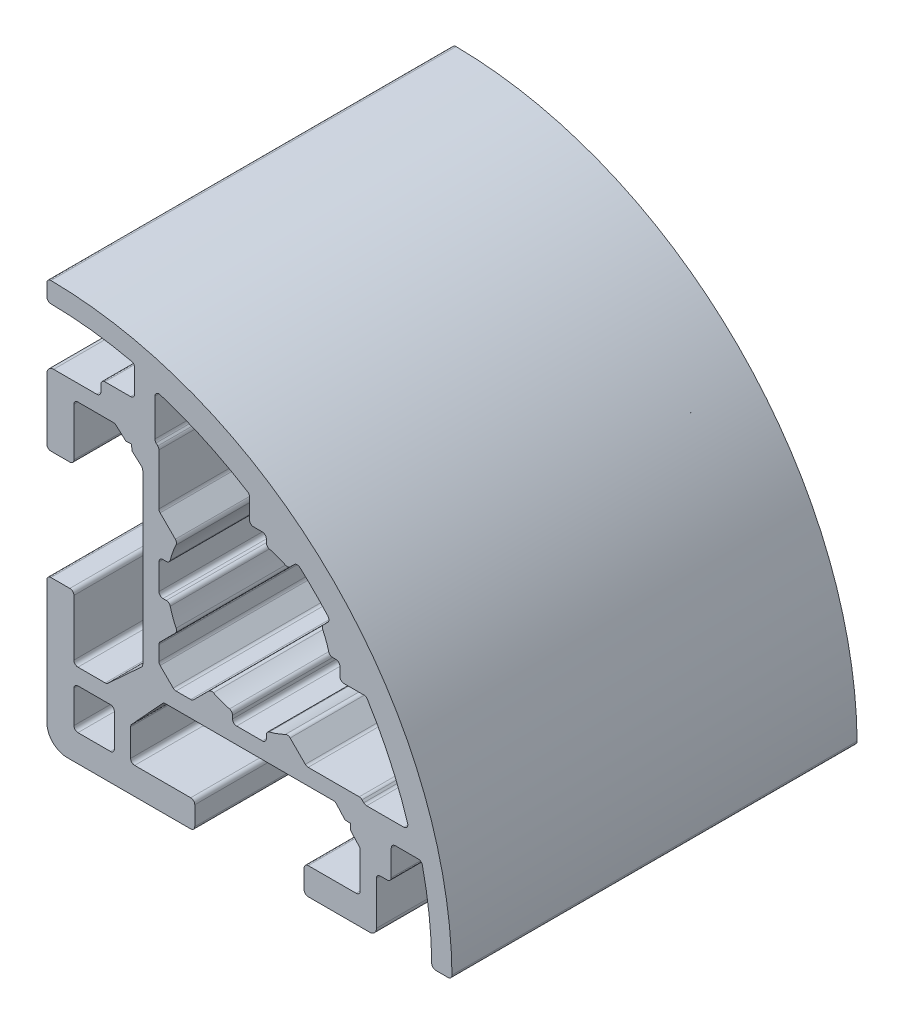
SolidWorks part; units mm, degrees
ref_plane "Plano frontal" through (0, 0, 0) normal (0, 0, 1) x (1, 0, 0)
ref_plane "Plano superior" through (0, 0, 0) normal (0, 1, 0) x (1, 0, 0)
ref_plane "Plano direito" through (0, 0, 0) normal (1, 0, 0) x (0, 0, -1)
ref_plane "Plano1" through (0, 0, 0) normal (0, 0, -1) x (-1, 0, 0)
sketch "Esboço1" plane through (0, 0, 0) normal (0, 0, -1) x (-1, 0, 0)
  line L0 (12.7, -13) -> (10.3, -13)
  line L1 (10, -12.7) -> (10, -10.3)
  line L2 (10.3, -10) -> (12.7, -10)
  line L3 (13, -10.3) -> (13, -12.7)
  line L4 (-0.95, 6.7) -> (-0.3, 6.7)
  line L5 (0, 7) -> (0, 8.4776)
  line L6 (7, 11.4273) -> (7, 8.6799)
  line L7 (6.9121, 8.4678) -> (6.7879, 8.3435)
  line L8 (6.7, 8.1314) -> (6.7, 4.3494)
  line L9 (6.6121, 4.1372) -> (5.4871, 3.0123)
  line L10 (6.1579, 1.25) -> (6.4, 1.25)
  line L11 (6.7, 0.95) -> (6.7, -0.95)
  line L12 (6.4, -1.25) -> (6.1579, -1.25)
  line L13 (5.4871, -3.0123) -> (6.6121, -4.1372)
  line L14 (6.7, -4.3494) -> (6.7, -5.4396)
  line L15 (6.6121, -5.6517) -> (5.6517, -6.6121)
  line L16 (5.4395, -6.7) -> (4.3494, -6.7)
  line L17 (4.1373, -6.6121) -> (3.0123, -5.4871)
  line L18 (1.25, -6.1579) -> (1.25, -6.4)
  line L19 (0.95, -6.7) -> (-0.95, -6.7)
  line L20 (-1.25, -6.4) -> (-1.25, -6.1579)
  line L21 (-3.0123, -5.4871) -> (-4.1373, -6.6121)
  line L22 (-4.3494, -6.7) -> (-8.1314, -6.7)
  line L23 (-8.3435, -6.7879) -> (-8.4678, -6.9121)
  line L24 (-8.6799, -7) -> (-11.4273, -7)
  line L25 (-8.4777, 0) -> (-7, 0)
  line L26 (-6.7, 0.3) -> (-6.7, 0.95)
  line L27 (-6.4, 1.25) -> (-6.1579, 1.25)
  line L28 (-5.4871, 3.0123) -> (-5.7974, 3.3226)
  line L29 (-3.3226, 5.7974) -> (-3.0123, 5.4871)
  line L30 (-1.25, 6.1579) -> (-1.25, 6.4)
  line L31 (7.9882, 6.432) -> (8.7045, 7.072)
  line L32 (8.7045, 7.072) -> (8.7283, 7.4958)
  line L33 (8.7283, 7.4958) -> (9.1516, 7.472)
  line L34 (9.1516, 7.472) -> (9.8678, 8.112)
  line L35 (10.08, 8.1999) -> (12.7001, 8.1998)
  line L36 (13.0001, 7.8998) -> (13, 4.3499)
  line L37 (13.3, 4.0499) -> (14.7, 4.0498)
  line L38 (15, 4.3498) -> (15, 8.8999)
  line L39 (14.5, 9.3999) -> (11.3, 9.3999)
  line L40 (11, 9.6999) -> (11, 10.1999)
  line L41 (10.7, 10.4999) -> (8.8, 10.4999)
  line L42 (8.5, 10.7999) -> (8.5, 12.51)
  line L43 (15, 13.7984) -> (15, 14.6985)
  line L44 (-14.6985, -15) -> (-13.7984, -15)
  line L45 (-12.5105, -8.5) -> (-10.8005, -8.5)
  line L46 (-10.5005, -8.8) -> (-10.5005, -10.7)
  line L47 (-10.2005, -11) -> (-9.7004, -11)
  line L48 (-9.4004, -11.3) -> (-9.4004, -14.5)
  line L49 (-8.9004, -15) -> (-4.3505, -15)
  line L50 (-4.0505, -14.7) -> (-4.0504, -13.3)
  line L51 (-4.3504, -13) -> (-7.9005, -12.9999)
  line L52 (-8.2005, -12.6999) -> (-8.2004, -10.0799)
  line L53 (-8.1126, -9.8677) -> (-7.4725, -9.1515)
  line L54 (-7.4725, -9.1515) -> (-7.4963, -8.728)
  line L55 (-7.4963, -8.728) -> (-7.0727, -8.7042)
  line L56 (-7.0727, -8.7042) -> (-6.4326, -7.988)
  line L57 (-6.2205, -7.9001) -> (6.2197, -7.9001)
  line L58 (6.4318, -7.988) -> (8.7117, -10.4679)
  line L59 (8.7996, -10.6801) -> (8.7996, -12.7001)
  line L60 (8.4996, -13.0001) -> (4.3496, -13.0001)
  line L61 (4.0496, -13.3001) -> (4.0496, -14.7)
  line L62 (4.3496, -15) -> (13.5, -15)
  line L63 (15, -13.5) -> (15, -4.3503)
  line L64 (14.7, -4.0503) -> (13.2999, -4.0503)
  line L65 (12.9999, -4.3503) -> (12.9999, -8.5003)
  line L66 (12.6999, -8.8003) -> (10.6798, -8.8003)
  line L67 (10.4677, -8.7124) -> (7.9878, -6.4325)
  line L68 (7.9003, -6.2203) -> (7.9003, 6.2198)
  arc A0 (10.3, -13) -> (10, -12.7) centre (10.3, -12.7) cw
  arc A1 (10, -10.3) -> (10.3, -10) centre (10.3, -10.3) cw
  arc A2 (12.7, -10) -> (13, -10.3) centre (12.7, -10.3) cw
  arc A3 (13, -12.7) -> (12.7, -13) centre (12.7, -12.7) cw
  arc A4 (-0.3, 6.7) -> (0, 7) centre (-0.3, 7) ccw
  arc A5 (0, 8.4776) -> (0.1408, 8.7319) centre (0.3, 8.4776) cw
  arc A6 (0.1408, 8.7319) -> (6.6101, 11.7135) centre (15, -15) cw
  arc A7 (6.6101, 11.7135) -> (7, 11.4273) centre (6.7, 11.4273) cw
  arc A8 (7, 8.6799) -> (6.9121, 8.4678) centre (6.7, 8.6799) cw
  arc A9 (6.7879, 8.3435) -> (6.7, 8.1314) centre (7, 8.1314) ccw
  arc A10 (6.7, 4.3494) -> (6.6121, 4.1372) centre (6.4, 4.3494) cw
  arc A11 (5.4871, 3.0123) -> (5.43, 2.6678) centre (5.6993, 2.8001) ccw
  arc A12 (5.43, 2.6678) -> (5.867, 1.4768) centre (0, 0) cw
  arc A13 (5.867, 1.4768) -> (6.1579, 1.25) centre (6.1579, 1.55) ccw
  arc A14 (6.4, 1.25) -> (6.7, 0.95) centre (6.4, 0.95) cw
  arc A15 (6.7, -0.95) -> (6.4, -1.25) centre (6.4, -0.95) cw
  arc A16 (6.1579, -1.25) -> (5.867, -1.4768) centre (6.1579, -1.55) ccw
  arc A17 (5.867, -1.4768) -> (5.43, -2.6678) centre (0, 0) cw
  arc A18 (5.43, -2.6678) -> (5.4871, -3.0123) centre (5.6993, -2.8001) ccw
  arc A19 (6.6121, -4.1372) -> (6.7, -4.3494) centre (6.4, -4.3494) cw
  arc A20 (6.7, -5.4396) -> (6.6121, -5.6517) centre (6.4, -5.4396) cw
  arc A21 (5.6517, -6.6121) -> (5.4395, -6.7) centre (5.4395, -6.4) cw
  arc A22 (4.3494, -6.7) -> (4.1373, -6.6121) centre (4.3494, -6.4) cw
  arc A23 (3.0123, -5.4871) -> (2.6678, -5.43) centre (2.8001, -5.6993) ccw
  arc A24 (2.6678, -5.43) -> (1.4768, -5.867) centre (0, 0) cw
  arc A25 (1.4768, -5.867) -> (1.25, -6.1579) centre (1.55, -6.1579) ccw
  arc A26 (1.25, -6.4) -> (0.95, -6.7) centre (0.95, -6.4) cw
  arc A27 (-0.95, -6.7) -> (-1.25, -6.4) centre (-0.95, -6.4) cw
  arc A28 (-1.25, -6.1579) -> (-1.4768, -5.867) centre (-1.55, -6.1579) ccw
  arc A29 (-1.4768, -5.867) -> (-2.6678, -5.43) centre (0, 0) cw
  arc A30 (-2.6678, -5.43) -> (-3.0123, -5.4871) centre (-2.8001, -5.6993) ccw
  arc A31 (-4.1373, -6.6121) -> (-4.3494, -6.7) centre (-4.3494, -6.4) cw
  arc A32 (-8.1314, -6.7) -> (-8.3435, -6.7879) centre (-8.1314, -7) ccw
  arc A33 (-8.4678, -6.9121) -> (-8.6799, -7) centre (-8.6799, -6.7) cw
  arc A34 (-11.4273, -7) -> (-11.7135, -6.6101) centre (-11.4273, -6.7) cw
  arc A35 (-11.7135, -6.6101) -> (-8.7319, -0.1408) centre (15, -15) cw
  arc A36 (-8.7319, -0.1408) -> (-8.4777, 0) centre (-8.4777, -0.3) cw
  arc A37 (-7, 0) -> (-6.7, 0.3) centre (-7, 0.3) ccw
  arc A38 (-6.7, 0.95) -> (-6.4, 1.25) centre (-6.4, 0.95) cw
  arc A39 (-6.1579, 1.25) -> (-5.867, 1.4768) centre (-6.1579, 1.55) ccw
  arc A40 (-5.867, 1.4768) -> (-5.43, 2.6678) centre (0, 0) cw
  arc A41 (-5.43, 2.6678) -> (-5.4871, 3.0123) centre (-5.6993, 2.8001) ccw
  arc A42 (-5.7974, 3.3226) -> (-5.8083, 3.7354) centre (-5.5853, 3.5347) cw
  arc A43 (-5.8083, 3.7354) -> (-3.7354, 5.8083) centre (15, -15) cw
  arc A44 (-3.7354, 5.8083) -> (-3.3226, 5.7974) centre (-3.5347, 5.5853) cw
  arc A45 (-3.0123, 5.4871) -> (-2.6678, 5.43) centre (-2.8001, 5.6993) ccw
  arc A46 (-2.6678, 5.43) -> (-1.4768, 5.867) centre (0, 0) cw
  arc A47 (-1.4768, 5.867) -> (-1.25, 6.1579) centre (-1.55, 6.1579) ccw
  arc A48 (-1.25, 6.4) -> (-0.95, 6.7) centre (-0.95, 6.4) cw
  arc A49 (9.8678, 8.112) -> (10.08, 8.1999) centre (10.08, 7.8999) cw
  arc A50 (12.7001, 8.1998) -> (13.0001, 7.8998) centre (12.7001, 7.8998) cw
  arc A51 (13, 4.3499) -> (13.3, 4.0499) centre (13.3, 4.3499) ccw
  arc A52 (14.7, 4.0498) -> (15, 4.3498) centre (14.7, 4.3498) ccw
  arc A53 (15, 8.8999) -> (14.5, 9.3999) centre (14.5, 8.8999) ccw
  arc A54 (11.3, 9.3999) -> (11, 9.6999) centre (11.3, 9.6999) cw
  arc A55 (11, 10.1999) -> (10.7, 10.4999) centre (10.7, 10.1999) ccw
  arc A56 (8.8, 10.4999) -> (8.5, 10.7999) centre (8.8, 10.7999) cw
  arc A57 (8.5, 12.51) -> (8.734, 12.8026) centre (8.8, 12.51) cw
  arc A58 (8.734, 12.8026) -> (14.7031, 13.4984) centre (15, -15) cw
  arc A59 (14.7031, 13.4984) -> (15, 13.7984) centre (14.7, 13.7984) ccw
  arc A60 (15, 14.6985) -> (14.697, 14.9985) centre (14.7, 14.6985) ccw
  arc A61 (14.697, 14.9985) -> (-14.9985, -14.697) centre (15, -15) ccw
  arc A62 (-14.9985, -14.697) -> (-14.6985, -15) centre (-14.6985, -14.7) ccw
  arc A63 (-13.7984, -15) -> (-13.4985, -14.7031) centre (-13.7984, -14.7) ccw
  arc A64 (-13.4985, -14.7031) -> (-12.8027, -8.734) centre (15, -15) cw
  arc A65 (-12.8027, -8.734) -> (-12.5105, -8.5) centre (-12.51, -8.8) cw
  arc A66 (-10.8005, -8.5) -> (-10.5005, -8.8) centre (-10.8005, -8.8) cw
  arc A67 (-10.5005, -10.7) -> (-10.2005, -11) centre (-10.2005, -10.7) ccw
  arc A68 (-9.7004, -11) -> (-9.4004, -11.3) centre (-9.7004, -11.3) cw
  arc A69 (-9.4004, -14.5) -> (-8.9004, -15) centre (-8.9004, -14.5) ccw
  arc A70 (-4.3505, -15) -> (-4.0505, -14.7) centre (-4.3505, -14.7) ccw
  arc A71 (-4.0504, -13.3) -> (-4.3504, -13) centre (-4.3504, -13.3) ccw
  arc A72 (-7.9005, -12.9999) -> (-8.2005, -12.6999) centre (-7.9005, -12.6999) cw
  arc A73 (-8.2004, -10.0799) -> (-8.1126, -9.8677) centre (-7.9004, -10.0799) cw
  arc A74 (-6.4326, -7.988) -> (-6.2205, -7.9001) centre (-6.2205, -8.2001) cw
  arc A75 (6.2197, -7.9001) -> (6.4318, -7.988) centre (6.2197, -8.2001) cw
  arc A76 (8.7117, -10.4679) -> (8.7996, -10.6801) centre (8.4996, -10.6801) cw
  arc A77 (8.7996, -12.7001) -> (8.4996, -13.0001) centre (8.4996, -12.7001) cw
  arc A78 (4.3496, -13.0001) -> (4.0496, -13.3001) centre (4.3496, -13.3001) ccw
  arc A79 (4.0496, -14.7) -> (4.3496, -15) centre (4.3496, -14.7) ccw
  arc A80 (13.5, -15) -> (15, -13.5) centre (13.5, -13.5) ccw
  arc A81 (15, -4.3503) -> (14.7, -4.0503) centre (14.7, -4.3503) ccw
  arc A82 (13.2999, -4.0503) -> (12.9999, -4.3503) centre (13.2999, -4.3503) ccw
  arc A83 (12.9999, -8.5003) -> (12.6999, -8.8003) centre (12.6999, -8.5003) cw
  arc A84 (10.6798, -8.8003) -> (10.4677, -8.7124) centre (10.6798, -8.5003) cw
  arc A85 (7.9878, -6.4325) -> (7.9003, -6.2203) centre (8.2003, -6.2208) cw
  arc A86 (7.9003, 6.2198) -> (7.9882, 6.432) centre (8.2003, 6.2198) cw
  dimension "D1" = 1.5
  dimension "D2" = 30
extrude "Ressalto-extrusão1" add sketch "Esboço1" against normal blind 30
